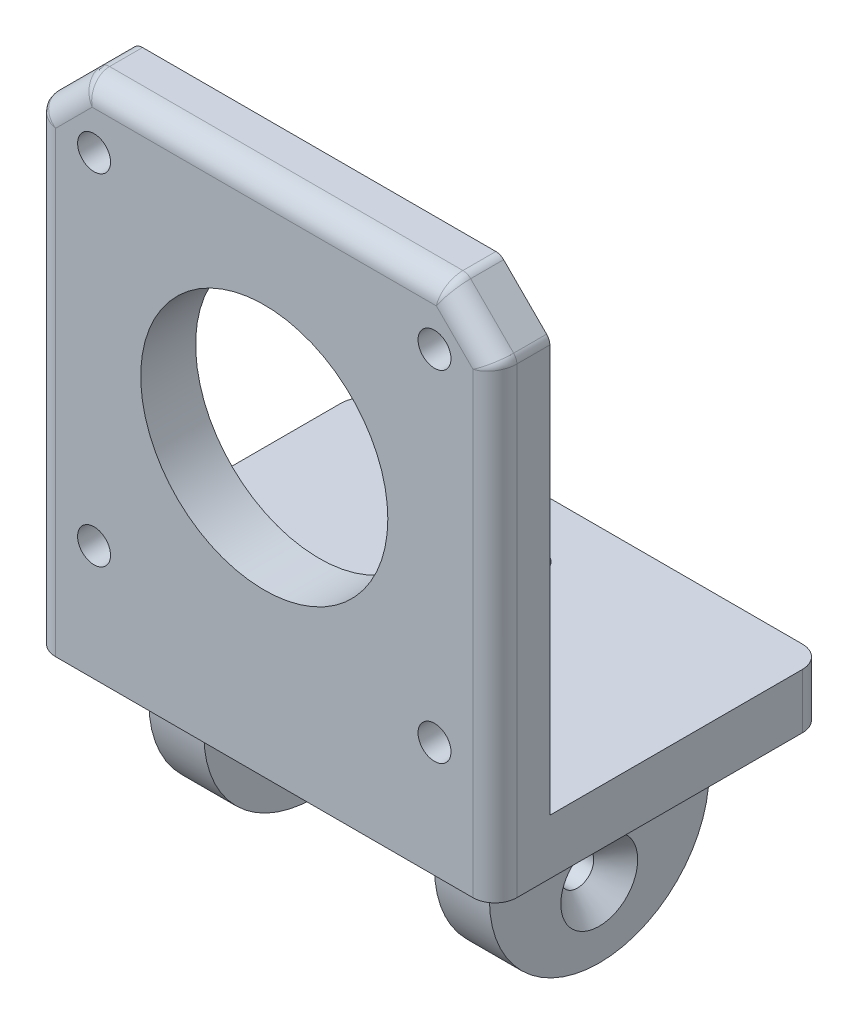
SolidWorks part; units mm, degrees
ref_plane "Plan de face" through (0, 0, 0) normal (0, 0, 1) x (1, 0, 0)
ref_plane "Plan de dessus" through (0, 0, 0) normal (0, 1, 0) x (1, 0, 0)
ref_plane "Plan de droite" through (0, 0, 0) normal (1, 0, 0) x (0, 0, -1)
sketch "Esquisse2" plane through (0, 0, 0) normal (0, 0, 1) x (1, 0, 0)
  line L6 (-21, -21) -> (16.0858, -21)
  line L7 (21, -21) -> (21, 16.0858)
  line L8 (20.7071, 16.7929) -> (16.7929, 20.7071)
  line L9 (16.0858, 21) -> (-16.0858, 21)
  line L10 (-16.7929, 20.7071) -> (-20.7071, 16.7929)
  line L11 (-21, 16.0858) -> (-21, -16.0858)
  line L12 (-21, -16.0858) -> (-21, -21)
  line L13 (16.0858, -21) -> (21, -21)
  arc A4 (21, 16.0858) -> (20.7071, 16.7929) centre (20, 16.0858) ccw
  arc A5 (16.7929, 20.7071) -> (16.0858, 21) centre (16.0858, 20) ccw
  arc A6 (-16.0858, 21) -> (-16.7929, 20.7071) centre (-16.0858, 20) ccw
  arc A7 (-20.7071, 16.7929) -> (-21, 16.0858) centre (-20, 16.0858) ccw
  circle A8 centre (0, 0) radius 11.25
  circle A9 centre (-15.5, 15.5) radius 1.5
  circle A11 centre (15.5, 15.5) radius 1.5
  circle A12 centre (15.5, -15.5) radius 1.5
  circle A13 centre (-15.5, -15.5) radius 1.5
extrude "Boss.-Extru.1" add sketch "Esquisse2" along normal blind 5
sketch "Esquisse3" plane through (0, -21, 0) normal (0, -1, 0) x (1, 0, 0)
  line L4 (-21, 0) -> (21, 0)
  line L5 (21, 0) -> (21, 5)
  line L6 (21, 5) -> (-21, 5)
  line L7 (-21, 5) -> (-21, 0)
  line L8 (-21, 0) -> (21, 0)
  line L9 (21, 0) -> (21, 5)
  line L10 (21, 5) -> (-21, 5)
  line L11 (-21, 5) -> (-21, 0)
  dimension "D1" = 0
extrude "Boss.-Extru.2" add sketch "Esquisse3" along normal blind 5
sketch "Esquisse4" plane through (0, 0, 0) normal (0, 0, -1) x (-1, 0, 0)
  line L0 (21, 16.0858) -> (21, -26) construction
  line L1 (-21, -26) -> (-21, 16.0858) construction
  line L2 (21, -26) -> (-21, -26) construction
  line L3 (21, -21) -> (21, -26)
  line L4 (-21, -26) -> (-21, -21)
  line L5 (21, -26) -> (-21, -26)
  line L6 (-21, -21) -> (21, -21)
  dimension "D1" = 5
extrude "Boss.-Extru.3" add sketch "Esquisse4" along normal blind 25
sketch "Esquisse5" plane through (0, -21, 0) normal (0, 1, 0) x (1, 0, 0)
  line L0 (0, 25) -> (0, 0) construction
  line L1 (-21, 25) -> (21, 25) construction
  line L2 (-21, 12.5) -> (21, 12.5) construction
  line L3 (-21, 25) -> (-21, 0) construction
  line L4 (21, 25) -> (21, 0) construction
  circle A0 centre (0, 19) radius 1.5
  circle A1 centre (0, 6) radius 1.5
  dimension "D2" = 3
  dimension "D1" = 6
extrude "Enlèv. mat.-Extru.1" cut sketch "Esquisse5" against normal blind 10
sketch "Esquisse6" plane through (0, 0, -25) normal (0, 0, -1) x (-1, 0, 0)
  line L0 (0, 41.8055) -> (0, -41.8055) construction
  line L2 (-10.5, -26) -> (-10.5, -40.4043)
  line L3 (-21, -26) -> (21, -26) construction
  line L4 (-10.5, -40.4043) -> (-15.5, -40.4043)
  line L5 (-15.5, -40.4043) -> (-15.5, -26)
  line L6 (-15.5, -26) -> (-10.5, -26)
  line L7 (15.5, -40.4043) -> (15.5, -26)
  line L8 (10.5, -40.4043) -> (15.5, -40.4043)
  line L9 (10.5, -26) -> (10.5, -40.4043)
  line L10 (15.5, -26) -> (10.5, -26)
  point P5 (0, 0)
  dimension "D1" = 10.5
  dimension "D2" = 5
extrude "Boss.-Extru.4" add sketch "Esquisse6" against normal blind 20 from offset 5 offset against normal yes
fillet "Congé1" radius 2 1 edges at (10.5, -26, -10) type face fillet first side face at (10.5, -33.2022, -10) second side face at (13, -26, -10)
fillet "Congé2" radius 2 1 edges at (15.5, -26, -10) type face fillet first side face at (15.5, -33.2022, -10) second side face at (12, -26, -10)
fillet "Congé3" radius 2 1 edges at (-10.5, -26, -10) type face fillet first side face at (-10.5, -33.2022, -10) second side face at (13, -26, -10)
fillet "Congé4" radius 2 1 edges at (-15.5, -26, -10) type face fillet first side face at (-15.5, -33.2022, -10) second side face at (13, -26, -10)
fillet "Congé5" 2 edges at (13, -40.4043, 0) (13, -40.4043, -20) type full round first side face at (13, -31.33, 0) second side face at (13, -31.33, -20) middle face at (13, -40.4043, -10)
fillet "Congé6" 2 edges at (-13, -40.4043, -20) (-13, -40.4043, 0) type full round first side face at (-13, -31.33, -20) second side face at (-13, -31.33, 0) middle face at (-13, -40.4043, -10)
sketch "Esquisse7" plane through (15.5, 0, 0) normal (1, 0, 0) x (0, 0, -1)
  line L0 (20, -28) -> (0, -28) construction
  circle A0 centre (10, -34) radius 1.5
  dimension "D2" = 3
  dimension "D1" = 6
extrude "Enlèv. mat.-Extru.2" cut sketch "Esquisse7" against normal through all
fillet "Congé7" radius 2 2 edges at (-21, -23.5, -25) (21, -23.5, -25)
fillet "Congé8" radius 2 9 edges at (21, -4.9571, 5) (20.9239, 16.4685, 5) (18.75, 18.75, 5) (16.4685, 20.9239, 5) (-21, -4.9571, 5) (-20.9239, 16.4685, 5) (-18.75, 18.75, 5) (-16.4685, 20.9239, 5) (0, 21, 5)
chamfer "Chanfrein1" distance 2 angle 45 2 edges at (-15.5, -35.5, -10) (15.5, -34, -11.5)
